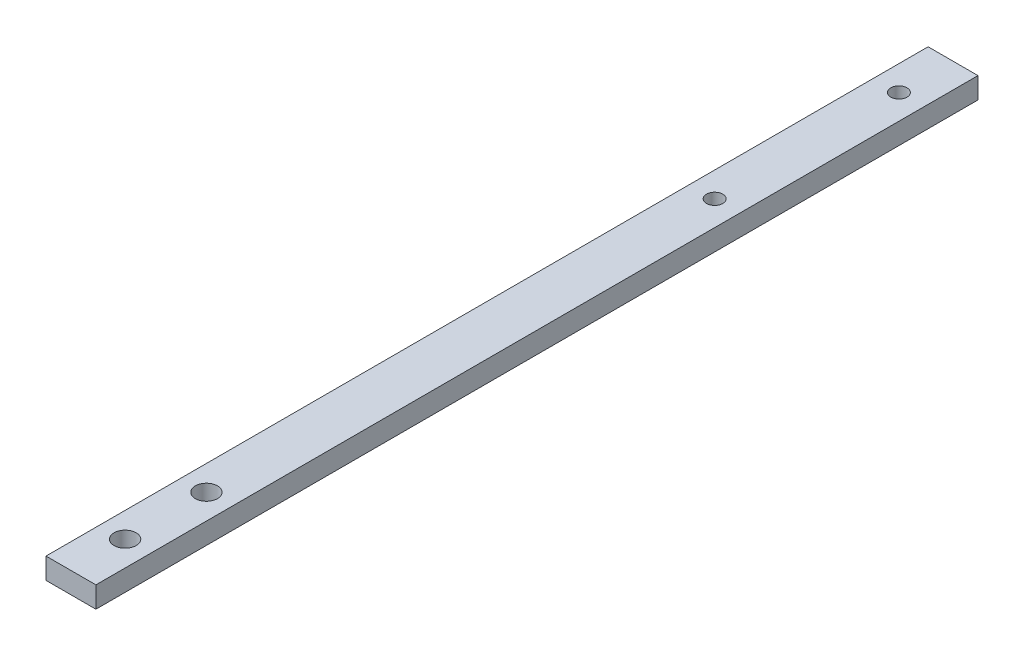
SolidWorks part; units mm, degrees
ref_plane "Front Plane" through (0, 0, 0) normal (0, 0, 1) x (1, 0, 0)
ref_plane "Top Plane" through (0, 0, 0) normal (0, 1, 0) x (1, 0, 0)
ref_plane "Right Plane" through (0, 0, 0) normal (1, 0, 0) x (0, 0, -1)
sketch "Sketch1" plane through (0, 0, 0) normal (0, 0, 1) x (1, 0, 0)
  circle A0 centre (0, 0) radius 2.5
  dimension "D1" = 5
extrude "Boss-Extrude1" add sketch "Sketch1" along normal blind 56
sketch "Sketch2" plane through (0, 0, 56) normal (0, 0, 1) x (1, 0, 0)
  line L1 (2.3024, -0.9741) -> (-2.3024, -0.9741)
  line L2 (2.3024, -0.9741) -> (2.3024, 0.9741)
  line L3 (2.3024, 0.9741) -> (-2.3024, 0.9741)
  line L4 (-2.3024, -0.9741) -> (-2.3024, 0.9741)
  line L5 (2.3024, -0.9741) -> (-2.3024, 0.9741) construction
  line L6 (2.3024, 0.9741) -> (-2.3024, -0.9741) construction
  circle A0 centre (0, 0) radius 2.5 construction
  point P0 (0, 0)
extrude "Boss-Extrude2" add sketch "Sketch2" along normal blind 25.4
sketch "Sketch3" plane through (0, 0.9741, 0) normal (0, 1, 0) x (1, 0, 0)
  line L0 (2.3024, -81.4) -> (-2.3024, -81.4) construction
  circle A0 centre (0, -68.9) radius 1.0227
  circle A1 centre (0, -76.4) radius 1.0227
  point P6 (0, -81.4)
  dimension "D1" = 5
  dimension "D2" = 12.5
extrude "Cut-Extrude1" cut sketch "Sketch3" against normal through all
sketch "Sketch4" plane through (0, 0, 0) normal (0, 1, 0) x (1, 0, 0)
  line L0 (0, 0) -> (0, -14.2164) construction
  line L1 (2.5, 0) -> (-2.5, 0) construction
  circle A0 centre (0, -5) radius 0.75
  circle A1 centre (0, -22) radius 0.75
  dimension "D1" = 1.5
  dimension "D2" = 1.5
  dimension "D3" = 17
  dimension "D4" = 5
extrude "Cut-Extrude2" cut sketch "Sketch4" against normal through all and the other way through all
sketch "Sketch5" plane through (0, 0, 81.4) normal (0, 0, 1) x (1, 0, 0)
  line L1 (-2.3024, 0.9741) -> (2.3024, 0.9741)
  line L2 (-2.3024, 0.9741) -> (-2.3024, -0.9741)
  line L3 (-2.3024, -0.9741) -> (2.3024, -0.9741)
  line L4 (2.3024, 0.9741) -> (2.3024, -0.9741)
extrude "Cut-Extrude3" cut sketch "Sketch5" against normal through all flip side to cut
